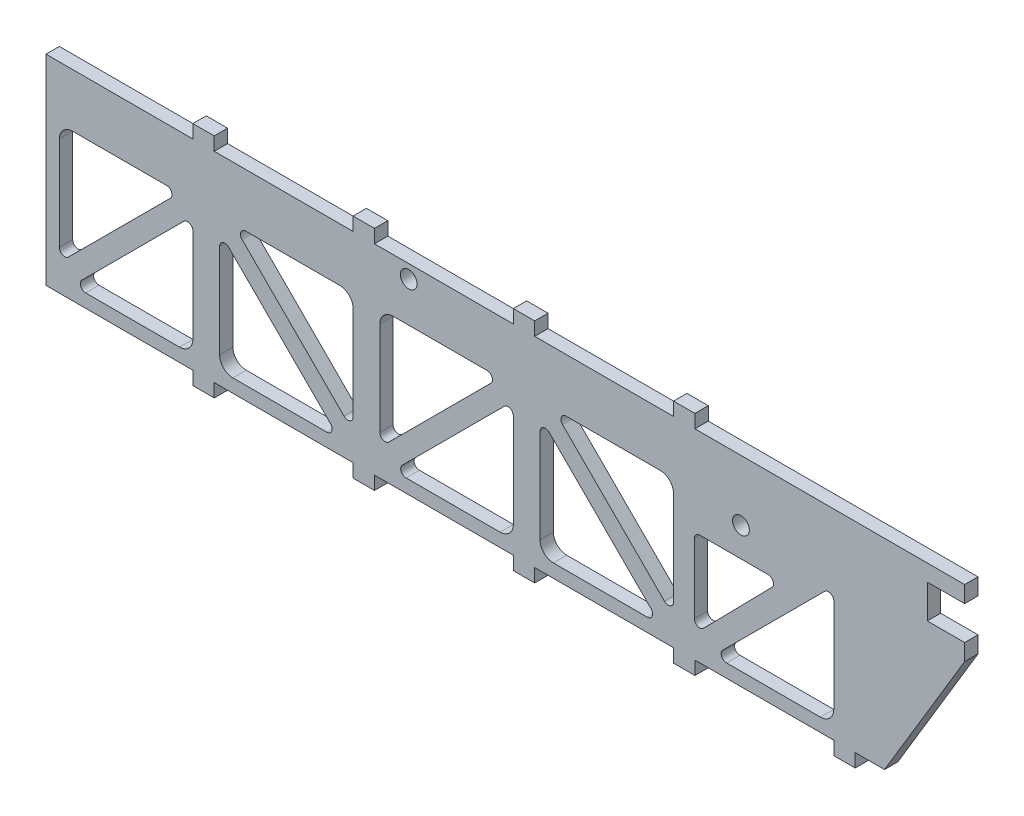
SolidWorks part; units mm, degrees
material "Pine"
ref_plane "Front Plane" through (0, 0, 0) normal (0, 0, 1) x (1, 0, 0)
ref_plane "Top Plane" through (0, 0, 0) normal (0, 1, 0) x (1, 0, 0)
ref_plane "Right Plane" through (0, 0, 0) normal (1, 0, 0) x (0, 0, -1)
sketch "Model" plane through (0, 0, 0) normal (0, 0, 1) x (1, 0, 0)
  line L0 (312.6855, 15.1239) -> (345.2281, 48.2988)
  line L1 (343.4149, 52.6175) -> (310.8722, 52.6175)
  line L2 (308.3322, 50.0775) -> (308.3322, 16.9026)
  line L8 (171.2321, 6.35) -> (215.9, 6.35)
  line L9 (217.9139, 59.1639) -> (169.4361, 10.6861)
  line L10 (222.25, 57.3679) -> (222.25, 12.7)
  line L11 (234.95, 57.3679) -> (234.95, 12.7)
  line L12 (239.2861, 59.1639) -> (287.7639, 10.6861)
  line L13 (241.3, 6.35) -> (285.9679, 6.35)
  line L14 (294.1139, 17.0361) -> (245.6361, 65.5139)
  line L15 (247.4321, 69.85) -> (292.1, 69.85)
  line L16 (298.45, 63.5) -> (298.45, 18.8321)
  line L17 (323.6321, 6.35) -> (368.3, 6.35)
  line L18 (370.3139, 59.1639) -> (321.8361, 10.6861)
  line L19 (374.65, 57.3679) -> (374.65, 12.7)
  line L20 (18.8321, 6.35) -> (63.5, 6.35)
  line L21 (17.0361, 10.6861) -> (65.5139, 59.1639)
  line L22 (69.85, 57.3679) -> (69.85, 12.7)
  line L23 (82.55, 57.3679) -> (82.55, 12.7)
  line L24 (86.8861, 59.1639) -> (135.3639, 10.6861)
  line L25 (88.9, 6.35) -> (133.5679, 6.35)
  line L26 (93.2361, 65.5139) -> (141.7139, 17.0361)
  line L27 (95.0321, 69.85) -> (139.7, 69.85)
  line L28 (146.05, 63.5) -> (146.05, 18.8321)
  line L29 (163.0861, 17.0361) -> (211.5639, 65.5139)
  line L30 (158.75, 63.5) -> (158.75, 18.8321)
  line L31 (165.1, 69.85) -> (209.7679, 69.85)
  line L35 (419.1, 87.376) -> (419.1, 71.374)
  line L36 (436.88, 87.376) -> (419.1, 87.376)
  line L37 (436.88, 87.376) -> (436.88, 95.25)
  line L38 (0, 95.25) -> (436.88, 95.25)
  line L39 (0, 0) -> (0, 95.25)
  line L40 (0, 0) -> (398.78, 0)
  line L41 (436.88, 63.5) -> (398.78, 0)
  line L42 (436.88, 63.5) -> (436.88, 71.374)
  line L43 (419.1, 71.374) -> (436.88, 71.374)
  line L44 (6.35, 63.5) -> (6.35, 18.8321)
  line L45 (12.7, 69.85) -> (57.3679, 69.85)
  line L46 (59.1639, 65.5139) -> (10.6861, 17.0361)
  arc A0 (215.9, 6.35) -> (222.25, 12.7) centre (215.9, 12.7) ccw
  arc A1 (169.4361, 10.6861) -> (171.2321, 6.35) centre (171.2321, 8.89) ccw
  arc A2 (222.25, 57.3679) -> (217.9139, 59.1639) centre (219.71, 57.3679) ccw
  arc A3 (239.2861, 59.1639) -> (234.95, 57.3679) centre (237.49, 57.3679) ccw
  arc A4 (285.9679, 6.35) -> (287.7639, 10.6861) centre (285.9679, 8.89) ccw
  arc A5 (234.95, 12.7) -> (241.3, 6.35) centre (241.3, 12.7) ccw
  arc A6 (247.4321, 69.85) -> (245.6361, 65.5139) centre (247.4321, 67.31) ccw
  arc A7 (298.45, 63.5) -> (292.1, 69.85) centre (292.1, 63.5) ccw
  arc A8 (294.1139, 17.0361) -> (298.45, 18.8321) centre (295.91, 18.8321) ccw
  arc A9 (321.8361, 10.6861) -> (323.6321, 6.35) centre (323.6321, 8.89) ccw
  arc A10 (374.65, 57.3679) -> (370.3139, 59.1639) centre (372.11, 57.3679) ccw
  arc A11 (368.3, 6.35) -> (374.65, 12.7) centre (368.3, 12.7) ccw
  arc A12 (63.5, 6.35) -> (69.85, 12.7) centre (63.5, 12.7) ccw
  arc A13 (17.0361, 10.6861) -> (18.8321, 6.35) centre (18.8321, 8.89) ccw
  arc A14 (69.85, 57.3679) -> (65.5139, 59.1639) centre (67.31, 57.3679) ccw
  arc A15 (86.8861, 59.1639) -> (82.55, 57.3679) centre (85.09, 57.3679) ccw
  arc A16 (133.5679, 6.35) -> (135.3639, 10.6861) centre (133.5679, 8.89) ccw
  arc A17 (82.55, 12.7) -> (88.9, 6.35) centre (88.9, 12.7) ccw
  arc A18 (95.0321, 69.85) -> (93.2361, 65.5139) centre (95.0321, 67.31) ccw
  arc A19 (146.05, 63.5) -> (139.7, 69.85) centre (139.7, 63.5) ccw
  arc A20 (141.7139, 17.0361) -> (146.05, 18.8321) centre (143.51, 18.8321) ccw
  arc A21 (158.75, 18.8321) -> (163.0861, 17.0361) centre (161.29, 18.8321) ccw
  arc A22 (165.1, 69.85) -> (158.75, 63.5) centre (165.1, 63.5) ccw
  arc A23 (211.5639, 65.5139) -> (209.7679, 69.85) centre (209.7679, 67.31) ccw
  arc A24 (345.2281, 48.2988) -> (343.4149, 52.6175) centre (343.4149, 50.0775) ccw
  arc A25 (310.8722, 52.6175) -> (308.3322, 50.0775) centre (310.8722, 50.0775) ccw
  arc A26 (312.6855, 15.1239) -> (308.3322, 16.9026) centre (310.8722, 16.9026) cw
  arc A27 (6.35, 18.8321) -> (10.6861, 17.0361) centre (8.89, 18.8321) ccw
  arc A28 (12.7, 69.85) -> (6.35, 63.5) centre (12.7, 63.5) ccw
  arc A29 (59.1639, 65.5139) -> (57.3679, 69.85) centre (57.3679, 67.31) ccw
  circle A30 centre (172.4917, 88.8013) radius 4
  circle A31 centre (330.4797, 66.4493) radius 4
  dimension "D2" = 6.4487
  dimension "D3" = 172.4917
  dimension "D4" = 8
  dimension "D5" = 22.352
  dimension "D6" = 8
  dimension "D8" = 2.54
  dimension "D1" = 95.25
  dimension "D7" = 157.988
extrude "Boss-Extrude2" add sketch "Model" along normal blind 6.35
sketch "Sketch1" plane through (0, 0, 6.35) normal (0, 0, 1) x (1, 0, 0)
  line L0 (69.85, 12.7) -> (69.85, 0) construction
  line L1 (146.05, 18.8321) -> (146.05, 0) construction
  line L2 (146.05, 18.8321) -> (146.05, 63.5) construction
  line L3 (0, 0) -> (398.78, 0) construction
  line L4 (222.25, 12.7) -> (222.25, 0) construction
  line L5 (222.25, 12.7) -> (222.25, 57.3679) construction
  line L6 (298.45, 18.8321) -> (298.45, 0) construction
  line L7 (146.05, 0) -> (156.21, 0)
  line L8 (69.85, 0) -> (80.01, 0)
  line L9 (69.85, 0) -> (69.85, -6.35)
  line L10 (69.85, -6.35) -> (80.01, -6.35)
  line L11 (80.01, 0) -> (80.01, -6.35)
  line L16 (222.25, 0) -> (232.41, 0)
  line L17 (222.25, 0) -> (222.25, -6.35)
  line L18 (222.25, -6.35) -> (232.41, -6.35)
  line L19 (232.41, 0) -> (232.41, -6.35)
  line L20 (146.05, 0) -> (146.05, -6.35)
  line L21 (146.05, -6.35) -> (156.21, -6.35)
  line L22 (156.21, 0) -> (156.21, -6.35)
  line L24 (374.65, 12.7) -> (374.65, 0) construction
  line L25 (374.65, 12.7) -> (374.65, 57.3679) construction
  line L26 (436.88, 95.25) -> (0, 95.25) construction
  line L27 (298.45, 0) -> (308.61, 0)
  line L28 (298.45, 0) -> (298.45, -6.35)
  line L29 (298.45, -6.35) -> (308.61, -6.35)
  line L30 (308.61, 0) -> (308.61, -6.35)
  line L31 (374.65, 0) -> (384.81, 0)
  line L32 (374.65, 0) -> (374.65, -6.35)
  line L33 (374.65, -6.35) -> (384.81, -6.35)
  line L34 (384.81, 0) -> (384.81, -6.35)
  line L35 (80.01, 95.25) -> (69.85, 95.25)
  line L36 (80.01, 95.25) -> (80.01, 101.6)
  line L37 (80.01, 101.6) -> (69.85, 101.6)
  line L38 (69.85, 95.25) -> (69.85, 101.6)
  line L40 (146.05, 95.25) -> (156.21, 95.25)
  line L41 (146.05, 95.25) -> (146.05, 101.6)
  line L42 (146.05, 101.6) -> (156.21, 101.6)
  line L43 (156.21, 95.25) -> (156.21, 101.6)
  line L44 (222.25, 95.25) -> (232.41, 95.25)
  line L45 (222.25, 95.25) -> (222.25, 101.6)
  line L46 (222.25, 101.6) -> (232.41, 101.6)
  line L47 (232.41, 95.25) -> (232.41, 101.6)
  line L48 (298.45, 95.25) -> (308.61, 95.25)
  line L49 (298.45, 95.25) -> (298.45, 101.6)
  line L50 (298.45, 101.6) -> (308.61, 101.6)
  line L51 (308.61, 95.25) -> (308.61, 101.6)
  arc A0 (368.3, 6.35) -> (374.65, 12.7) centre (368.3, 12.7) ccw construction
  dimension "D1" = 10.16
  dimension "D2" = 6.35
  dimension "D3" = 10.16
  dimension "D4" = 6.35
  dimension "D5" = 10.16
  dimension "D6" = 10.16
  dimension "D7" = 10.16
  dimension "D8" = 6.35
  dimension "D9" = 10.16
  dimension "D10" = 10.16
  dimension "D11" = 10.16
  dimension "D12" = 10.16
extrude "Boss-Extrude3" add sketch "Sketch1" against normal up to surface (6.35 mm away) up to face at (321.5295, 39.2174, 0)
